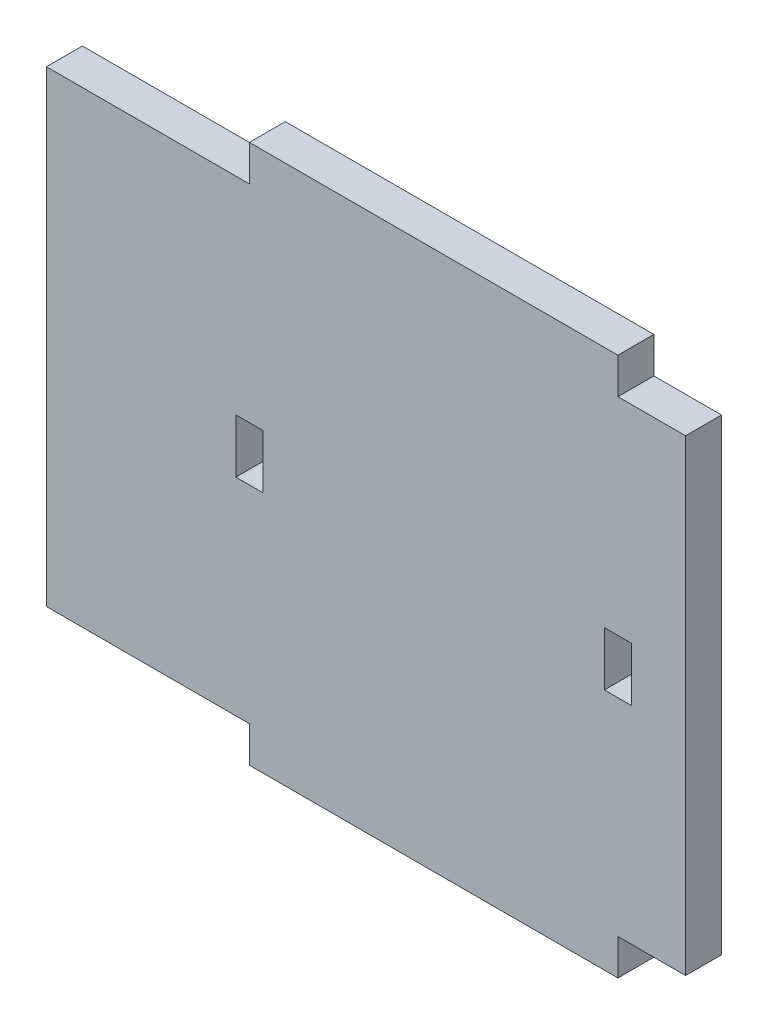
SolidWorks part; units mm, degrees
ref_plane "Front Plane" through (0, 0, 0) normal (0, 0, 1) x (1, 0, 0)
ref_plane "Top Plane" through (0, 0, 0) normal (0, 1, 0) x (1, 0, 0)
ref_plane "Right Plane" through (0, 0, 0) normal (1, 0, 0) x (0, 0, -1)
sketch "Sketch1" plane through (0, 0, 0) normal (0, 0, 1) x (1, 0, 0)
  line L0 (-13.2632, 0) -> (27.7368, 0)
  line L1 (27.7368, 0) -> (27.7368, 4)
  line L2 (27.7368, 4) -> (35.2668, 4)
  line L3 (35.2668, 4) -> (35.2668, 56)
  line L4 (35.2668, 56) -> (27.7368, 56)
  line L5 (27.7368, 56) -> (27.7368, 60)
  line L6 (27.7368, 60) -> (-13.2632, 60)
  line L7 (-13.2632, 60) -> (-13.2632, 56)
  line L8 (-13.2632, 56) -> (-35.8332, 56)
  line L9 (-35.8332, 56) -> (-35.8332, 4)
  line L10 (-35.8332, 4) -> (-13.2632, 4)
  line L11 (-13.2632, 4) -> (-13.2632, 0)
  dimension "D1" = 22.57
  dimension "D2" = 7.53
  dimension "D3" = 41
  dimension "D4" = 52
  dimension "D6" = 4
extrude "Boss-Extrude1" add sketch "Sketch1" along normal blind 4
sketch "Sketch2" plane through (0, 0, 4) normal (0, 0, 1) x (1, 0, 0)
  line L0 (-35.8332, 30) -> (35.2668, 30) construction
  line L1 (-14.7632, 33) -> (-11.7632, 33)
  line L2 (-14.7632, 33) -> (-14.7632, 27)
  line L3 (-14.7632, 27) -> (-11.7632, 27)
  line L4 (-11.7632, 33) -> (-11.7632, 27)
  line L5 (-35.8332, 56) -> (-35.8332, 4) construction
  line L6 (35.2668, 4) -> (35.2668, 56) construction
  line L7 (7.2368, 0) -> (7.2368, 60) construction
  line L8 (-13.2632, 0) -> (27.7368, 0) construction
  line L9 (27.7368, 60) -> (-13.2632, 60) construction
  line L10 (29.2368, 27) -> (26.2368, 27)
  line L11 (29.2368, 33) -> (26.2368, 33)
  line L12 (26.2368, 33) -> (26.2368, 27)
  line L13 (29.2368, 33) -> (29.2368, 27)
  dimension "D1" = 6
  dimension "D2" = 3
  dimension "D3" = 19
extrude "Cut-Extrude1" cut sketch "Sketch2" against normal blind 10
